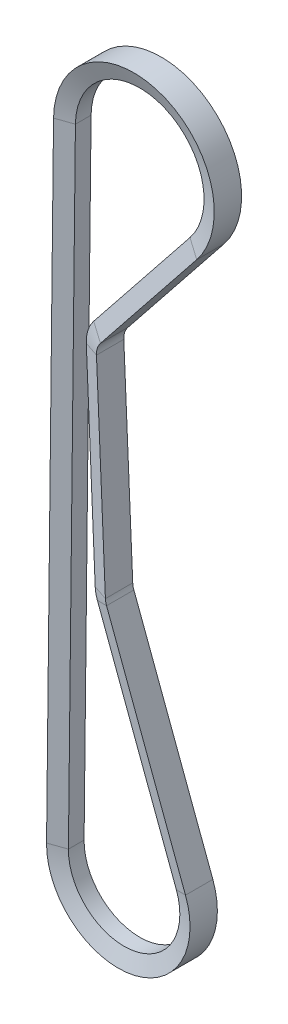
SolidWorks part; units mm, degrees
ref_plane "Front Plane" through (0, 0, 0) normal (0, 0, 1) x (1, 0, 0)
ref_plane "Top Plane" through (0, 0, 0) normal (0, 1, 0) x (1, 0, 0)
ref_plane "Right Plane" through (0, 0, 0) normal (1, 0, 0) x (0, 0, -1)
sketch "Sketch2" plane through (0, 0, 0) normal (0, 0, 1) x (1, 0, 0)
  line L0 (0, 0) -> (1, 0) construction
  line L1 (0, 0) -> (0, 1) construction
  line L9 (27.3208, 202.4641) -> (-6.2228, 160.445)
  line L10 (-7.6043, 156.2091) -> (-4.4944, 84.2763)
  line L11 (-4.0979, 82.3262) -> (23.416, 8.7573)
  line L12 (-24.9985, 0.2771) -> (-22.56, 220.2432)
  arc A4 (-22.56, 220.2432) -> (27.3208, 202.4641) centre (5.4383, 219.9328) cw
  arc A5 (-6.2228, 160.445) -> (-7.6043, 156.2091) centre (-1.2602, 156.4834) ccw
  arc A6 (-4.4944, 84.2763) -> (-4.0979, 82.3262) centre (1.8497, 84.5505) ccw
  arc A7 (23.416, 8.7573) -> (-24.9985, 0.2771) centre (0, 0) cw
ref_plane "Plane4" through (23.416, 8.7573, 0) normal (0.3503, -0.9366, 0) x (0, 0, -1)
sketch "Sketch3" plane through (23.416, 8.7573, 0) normal (0.3503, -0.9366, 0) x (0, 0, -1)
  line L0 (-4.7625, 0) -> (4.7625, 0)
  line L1 (-4.7625, 0) -> (-2.7286, -5.588)
  line L2 (-2.7286, -5.588) -> (2.7286, -5.588)
  line L3 (2.7286, -5.588) -> (4.7625, 0)
  line L4 (0, 0) -> (0, -5.588) construction
  dimension "D1" = 9.525
  dimension "D2" = 5.588
  dimension "D3" = 40
sweep "Sweep1" add profiles "Sketch3" path "Sketch2"
